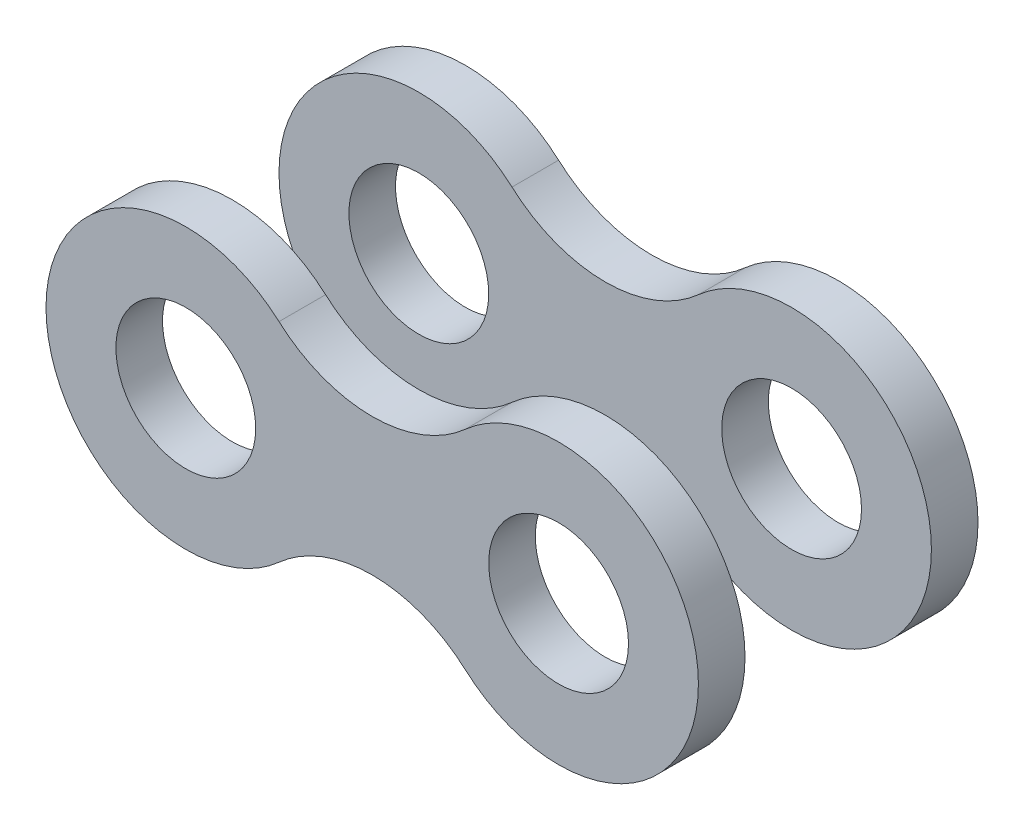
SolidWorks part; units mm, degrees
ref_plane "Front Plane" through (0, 0, 0) normal (0, 0, 1) x (1, 0, 0)
ref_plane "Top Plane" through (0, 0, 0) normal (0, 1, 0) x (1, 0, 0)
ref_plane "Right Plane" through (0, 0, 0) normal (1, 0, 0) x (0, 0, -1)
sketch "Sketch2" plane through (0, 0, 0) normal (0, 0, 1) x (1, 0, 0)
  circle A0 centre (0, 0) radius 2.3813
  circle A1 centre (6.35, 0) radius 2.3813
  arc A2 (1.5875, 1.7749) -> (4.7625, 1.7749) centre (3.175, 3.5498) ccw
  arc A3 (1.5875, -1.7749) -> (4.7625, -1.7749) centre (3.175, -3.5498) cw
  circle A4 centre (0, 0) radius 1.1906
  circle A5 centre (6.35, 0) radius 1.1906
  dimension "D2" = 4.7625
  dimension "D3" = 2.3813
  dimension "D1" = 6.35
extrude "Boss-Extrude1" add sketch "Sketch2" along normal blind 0.7937 contours A0 A4 | A0 A3 A1 A2 | A1 A5 region at (2.1123, -0.9446, 0) region at (3.175, 0, 0) region at (7.2946, 2.1123, 0)
sketch "Sketch3" plane through (0, 0, 0) normal (0, 0, -1) x (-1, 0, 0)
  circle A0 centre (-6.35, 0) radius 2.6988
  arc A1 (-4.7625, 1.7749) -> (-4.7625, -1.7749) centre (-6.35, 0) ccw construction
  circle A2 centre (-12.7, 0) radius 2.6987
  arc A3 (-11.1125, 2.1825) -> (-7.9375, 2.1825) centre (-9.525, 4.3649) ccw
  arc A4 (-11.1125, -2.1825) -> (-7.9375, -2.1825) centre (-9.525, -4.3649) cw
  circle A5 centre (-6.35, 0) radius 1.1906 construction
  circle A6 centre (-6.35, 0) radius 1.1906
  circle A7 centre (-12.7, 0) radius 1.1906
  arc M5 (-1.5875, 1.7749) -> (-4.7625, 1.7749) centre (-3.175, 3.5498) cw
  arc M6 (-4.7625, 1.7749) -> (-4.7625, -1.7749) centre (-6.35, 0) ccw
  arc M7 (-4.7625, -1.7749) -> (-1.5875, -1.7749) centre (-3.175, -3.5498) cw
  circle M8 centre (-6.35, 0) radius 1.1906
  dimension "D1" = 0.3175
  dimension "D2" = 6.35
extrude "Boss-Extrude2" add sketch "Sketch3" along normal blind 0.7937 separate body contours A2 A7 | A0 M7 M5 M6 M8 | A0 M5 M7 M6 | A2 A4 A0 A3 region at (5.7852, 2.5633, 0) region at (9.525, 0, 0) region at (3.8053, 0.6609, 0) region at (10.3631, 1.1899, 0)
extrude "Boss-Extrude3" add sketch "Sketch3<4>" against normal blind 3.175 from surface contours M8 | A7 region at (6.35, 0, 0) region at (12.7, 0, 0) starting at face at (9.525, 0, -0.7937)
sketch "Sketch3<4>" plane through (0, 0, 0) normal (0, 0, -1) x (-1, 0, 0) same geometry as "Sketch3"
mirror "Mirror1" about plane through (6.35, 0, 2.3812) normal (0, 0, -1) of bodies 105 101
combine bodies "Combine1" operation type add bodies to combine 105 106
delete or keep bodies "Body-Delete/Keep 1" type delete bodies bodies 108
ref_plane "Plane1" through (0, 0, 2.3812) normal (0, 0, 1) x (1, 0, 0)
